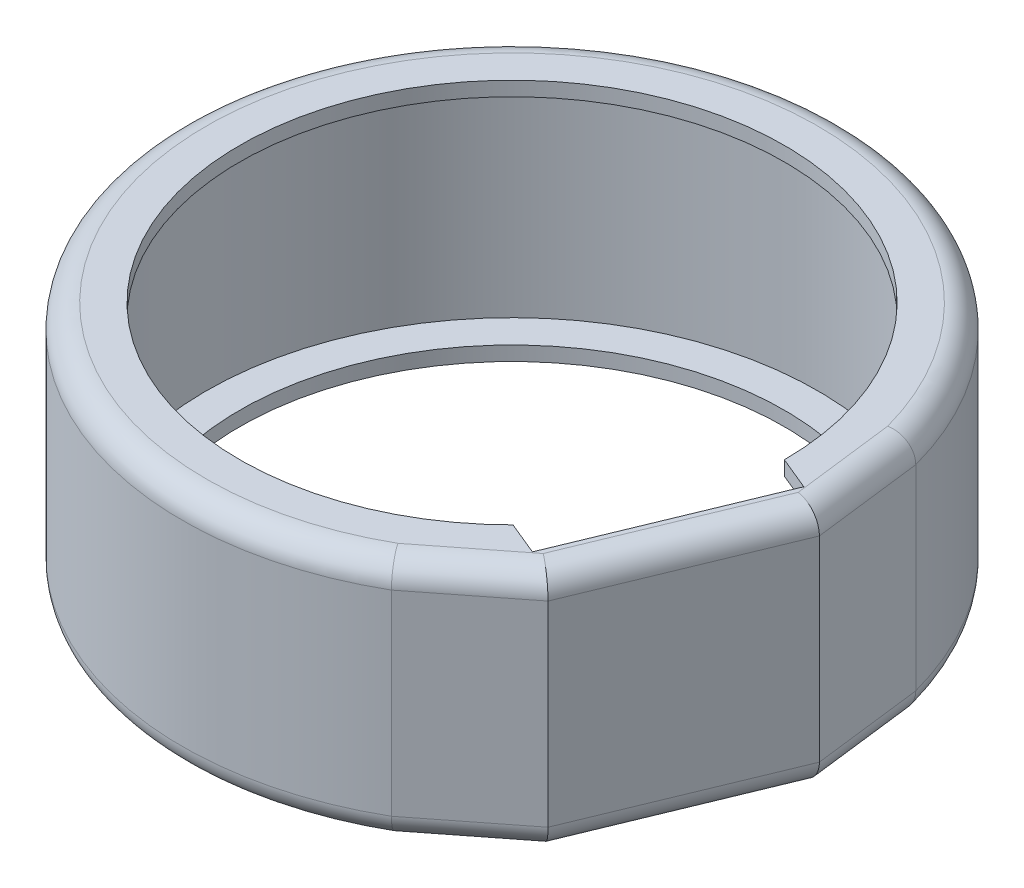
SolidWorks part; units mm, degrees
ref_plane "前视基准面" through (0, 0, 0) normal (0, 0, 1) x (1, 0, 0)
ref_plane "上视基准面" through (0, 0, 0) normal (0, 1, 0) x (1, 0, 0)
ref_plane "右视基准面" through (0, 0, 0) normal (1, 0, 0) x (0, 0, -1)
sketch "草图1" plane through (0, 0, 0) normal (0, 1, 0) x (1, 0, 0)
  line L0 (0, 0) -> (11.4, 0) construction
  line L1 (0, 0) -> (8.0803, -8.0417) construction
  line L2 (11.4, 0) -> (8.0803, -8.0417)
  line L6 (0, 0) -> (13.3298, 3.5717) construction
  line L7 (0, 0) -> (6.9, -11.9512) construction
  line L10 (11.4, 0) -> (14.582, -1.3136) construction
  line L13 (11.4, 0) -> (8.0707, -8.0378)
  line L15 (8.0707, -8.0378) -> (8.0803, -8.0417)
  line L17 (11.4, 0) -> (8.0803, -8.0417)
  line L20 (13.8957, -1.0303) -> (10.576, -9.072)
  line L21 (13.8957, -1.0303) -> (13.3298, 3.5717)
  line L22 (10.576, -9.072) -> (6.9, -11.9512)
  arc A0 (11.4, 0) -> (8.0803, -8.0417) centre (0, 0) ccw
  arc A3 (13.3298, 3.5717) -> (6.9, -11.9512) centre (0, 0) ccw
extrude "凸台-拉伸1" add sketch "草图1" along normal blind 0.6 contours A3 A0 L2 region at (11.8744, 0, 4.9019)
sketch "草图2" plane through (0, 0, 0) normal (0, -1, 0) x (-1, 0, 0)
  line L5 (0, 0) -> (-6.9, -11.9512) construction
  line L7 (0, 0) -> (-13.3298, 3.5717) construction
  line L9 (-9.4481, -8.6356) -> (-12.7871, -0.5746)
  line L10 (0, 0) -> (-11.4, 0) construction
  line L14 (-13.8957, -1.0303) -> (-10.576, -9.072)
  line L16 (-10.576, -9.072) -> (-6.9, -11.9512)
  line L17 (-13.8957, -1.0303) -> (-13.3298, 3.5717)
  arc A0 (-6.9, -11.9512) -> (-13.3298, 3.5717) centre (0, 0) ccw
  arc A1 (-9.4481, -8.6356) -> (-12.7871, -0.5746) centre (0, 0) ccw
extrude "凸台-拉伸3" add sketch "草图2" along normal blind 9
sketch "草图5" plane through (0, -9, 0) normal (0, -1, 0) x (-1, 0, 0)
  line L0 (-8.0803, -8.0417) -> (-11.4, 0)
  line L3 (-10.576, -9.072) -> (-13.8957, -1.0303)
  line L4 (0, 0) -> (-6.9, -11.9512) construction
  line L5 (0, 0) -> (-13.3298, 3.5717) construction
  line L6 (-6.9, -11.9512) -> (-10.576, -9.072)
  line L7 (-13.8957, -1.0303) -> (-13.3298, 3.5717)
  line L9 (-8.0803, -8.0417) -> (-11.4, 0)
  line L12 (-10.576, -9.072) -> (-13.8957, -1.0303)
  arc A0 (-8.0803, -8.0417) -> (-11.4, 0) centre (0, 0) ccw
  arc A1 (-6.9, -11.9512) -> (-13.3298, 3.5717) centre (0, 0) ccw
  arc M13 (-6.9, -11.9512) -> (-13.3298, 3.5717) centre (0, 0) ccw
  line M14 (-13.3298, 3.5717) -> (-13.8957, -1.0303)
  line M15 (-13.8957, -1.0303) -> (-10.576, -9.072)
  line M16 (-10.576, -9.072) -> (-6.9, -11.9512)
  line M17 (-9.4481, -8.6356) -> (-12.7871, -0.5746)
  arc M18 (-12.7871, -0.5746) -> (-9.4481, -8.6356) centre (0, 0) cw
extrude "凸台-拉伸4" add sketch "草图5" along normal blind 0.6 contours M16 M13 M14 M15 M18 M17 | A0 L0 M17 M18 region at (11.8744, -9, 4.9019) region at (10.7831, -9, 4.4665)
fillet "圆角1" radius 1 4 edges at (13.6127, -9.6, -1.2707) (-12.7495, -9.6, -5.281) (8.738, -9.6, 10.5116) (12.2358, -9.6, 5.0511) type face fillet first side face at (13.6127, -4.5, -1.2707) first side face at (12.2358, -4.5, 5.0511) first side face at (8.738, -4.5, 10.5116) first side face at (-1.3173, -4.5, -0.5457) second side face at (5.4593, -9.6, 2.2527)
fillet "圆角2" radius 1 4 edges at (13.6127, 0.6, -1.2707) (-12.7495, 0.6, -5.281) (8.738, 0.6, 10.5116) (12.2358, 0.6, 5.0511) type face fillet first side face at (13.6127, -4, -1.2707) first side face at (12.2358, -4, 5.0511) first side face at (8.738, -4, 10.5116) first side face at (-1.3173, -4, -0.5457) second side face at (-0.3987, 0.6, -0.1646)
sketch "草图7" plane through (9.7401, 0, 4.0209) normal (-0.9243, 0, -0.3816) x (-0.3816, 0, 0.9243)
  line L0 (-4.35, 0.6) -> (-4.35, 0)
  line L1 (-4.35, 0.6) -> (4.35, 0.6)
  line L2 (-4.35, 0) -> (4.35, 0)
  line L3 (4.35, 0.6) -> (4.35, 0)
extrude "切除-拉伸1" cut sketch "草图7" against normal blind 1.5
